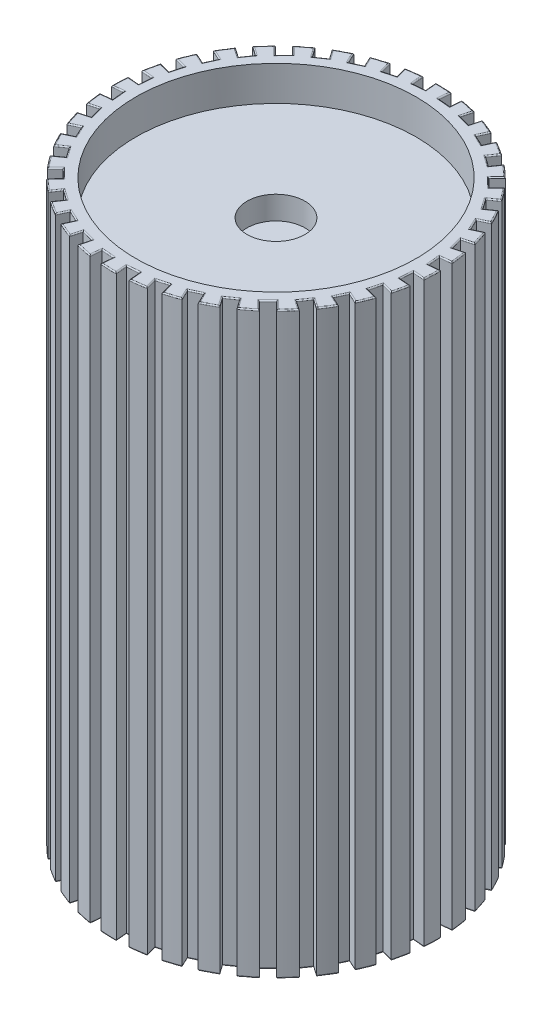
SolidWorks part; units mm, degrees
ref_plane "Front Plane" through (0, 0, 0) normal (0, 0, 1) x (1, 0, 0)
ref_plane "Top Plane" through (0, 0, 0) normal (0, 1, 0) x (1, 0, 0)
ref_plane "Right Plane" through (0, 0, 0) normal (1, 0, 0) x (0, 0, -1)
other "Configuration Table"
sketch "草图1" plane through (0, 0, 0) normal (0, 1, 0) x (1, 0, 0)
  circle A0 centre (0, 0) radius 13
  dimension "D1" = 26
extrude "凸台-拉伸1" add sketch "草图1" along normal blind 50
sketch "草图6" plane through (0, 50, 0) normal (0, 1, 0) x (1, 0, 0)
  circle A0 centre (0, 0) radius 14
  dimension "D1" = 28
extrude "凸台-拉伸4" add sketch "草图6" against normal through all
sketch "草图2" plane through (0, 50, 0) normal (0, 1, 0) x (1, 0, 0)
  circle A0 centre (0, 0) radius 12
  dimension "D1" = 24
extrude "切除-拉伸1" cut sketch "草图2" against normal blind 3
sketch "草图7" plane through (0, 50, 0) normal (0, 1, 0) x (1, 0, 0)
  line L0 (-15.6468, 4.1422) -> (-12.5671, 3.3269)
  line L1 (-15.6468, 4.1422) -> (-15.3762, 5.1646)
  line L2 (-12.5671, 3.3269) -> (-12.2964, 4.3493)
  line L3 (-15.3762, 5.1646) -> (-12.2964, 4.3493)
  line L4 (-14.6898, 6.7963) -> (-11.7985, 5.4586)
  line L5 (-14.6898, 6.7963) -> (-14.2457, 7.7562)
  line L6 (-14.2457, 7.7562) -> (-11.3544, 6.4185)
  line L7 (-11.7985, 5.4586) -> (-11.3544, 6.4185)
  line L8 (-13.2865, 9.2439) -> (-10.6713, 7.4245)
  line L9 (-13.2865, 9.2439) -> (-12.6825, 10.1121)
  line L10 (-12.6825, 10.1121) -> (-10.0673, 8.2926)
  line L11 (-10.6713, 7.4245) -> (-10.0673, 8.2926)
  line L12 (-11.4794, 11.4107) -> (-9.22, 9.1647)
  line L13 (-11.4794, 11.4107) -> (-10.7338, 12.1608)
  line L14 (-10.7338, 12.1608) -> (-8.4744, 9.9148)
  line L15 (-9.22, 9.1647) -> (-8.4744, 9.9148)
  line L16 (-9.3236, 13.2307) -> (-7.4884, 10.6265)
  line L17 (-9.3236, 13.2307) -> (-8.4591, 13.8399)
  line L18 (-8.4591, 13.8399) -> (-6.6239, 11.2358)
  line L19 (-7.4884, 10.6265) -> (-6.6239, 11.2358)
  line L20 (-6.8845, 14.6487) -> (-5.5294, 11.7654)
  line L21 (-6.8845, 14.6487) -> (-5.9273, 15.0986)
  line L22 (-5.9273, 15.0986) -> (-4.5722, 12.2153)
  line L23 (-5.5294, 11.7654) -> (-4.5722, 12.2153)
  line L24 (-4.2361, 15.6217) -> (-3.4024, 12.5469)
  line L25 (-4.2361, 15.6217) -> (-3.2154, 15.8985)
  line L26 (-3.2154, 15.8985) -> (-2.3816, 12.8237)
  line L27 (-3.4024, 12.5469) -> (-2.3816, 12.8237)
  line L28 (-1.4591, 16.1199) -> (-1.1719, 12.9471)
  line L29 (-1.4591, 16.1199) -> (-0.4058, 16.2153)
  line L30 (-0.4058, 16.2153) -> (-0.1186, 13.0424)
  line L31 (-1.1719, 12.9471) -> (-0.1186, 13.0424)
  line L32 (1.3622, 16.1284) -> (1.0941, 12.9539)
  line L33 (1.3622, 16.1284) -> (2.4161, 16.0394)
  line L34 (2.4161, 16.0394) -> (2.148, 12.8649)
  line L35 (1.0941, 12.9539) -> (2.148, 12.8649)
  line L36 (4.1422, 15.6468) -> (3.3269, 12.5671)
  line L37 (4.1422, 15.6468) -> (5.1646, 15.3762)
  line L38 (5.1646, 15.3762) -> (4.3493, 12.2964)
  line L39 (3.3269, 12.5671) -> (4.3493, 12.2964)
  line L40 (6.7963, 14.6898) -> (5.4586, 11.7985)
  line L41 (6.7963, 14.6898) -> (7.7562, 14.2457)
  line L42 (7.7562, 14.2457) -> (6.4185, 11.3544)
  line L43 (5.4586, 11.7985) -> (6.4185, 11.3544)
  line L44 (9.2439, 13.2865) -> (7.4245, 10.6713)
  line L45 (9.2439, 13.2865) -> (10.1121, 12.6825)
  line L46 (10.1121, 12.6825) -> (8.2926, 10.0673)
  line L47 (7.4245, 10.6713) -> (8.2926, 10.0673)
  line L48 (11.4107, 11.4794) -> (9.1647, 9.22)
  line L49 (11.4107, 11.4794) -> (12.1608, 10.7338)
  line L50 (12.1608, 10.7338) -> (9.9148, 8.4744)
  line L51 (9.1647, 9.22) -> (9.9148, 8.4744)
  line L52 (13.2307, 9.3236) -> (10.6265, 7.4884)
  line L53 (13.2307, 9.3236) -> (13.8399, 8.4591)
  line L54 (13.8399, 8.4591) -> (11.2358, 6.6239)
  line L55 (10.6265, 7.4884) -> (11.2358, 6.6239)
  line L56 (14.6487, 6.8845) -> (11.7654, 5.5294)
  line L57 (14.6487, 6.8845) -> (15.0986, 5.9273)
  line L58 (15.0986, 5.9273) -> (12.2153, 4.5722)
  line L59 (11.7654, 5.5294) -> (12.2153, 4.5722)
  line L60 (15.6217, 4.2361) -> (12.5469, 3.4024)
  line L61 (15.6217, 4.2361) -> (15.8985, 3.2154)
  line L62 (15.8985, 3.2154) -> (12.8237, 2.3816)
  line L63 (12.5469, 3.4024) -> (12.8237, 2.3816)
  line L64 (16.1199, 1.4591) -> (12.9471, 1.1719)
  line L65 (16.1199, 1.4591) -> (16.2153, 0.4058)
  line L66 (16.2153, 0.4058) -> (13.0424, 0.1186)
  line L67 (12.9471, 1.1719) -> (13.0424, 0.1186)
  line L68 (16.1284, -1.3622) -> (12.9539, -1.0941)
  line L69 (16.1284, -1.3622) -> (16.0394, -2.4161)
  line L70 (16.0394, -2.4161) -> (12.8649, -2.148)
  line L71 (12.9539, -1.0941) -> (12.8649, -2.148)
  line L72 (15.6468, -4.1422) -> (12.5671, -3.3269)
  line L73 (15.6468, -4.1422) -> (15.3762, -5.1646)
  line L74 (15.3762, -5.1646) -> (12.2964, -4.3493)
  line L75 (12.5671, -3.3269) -> (12.2964, -4.3493)
  line L76 (14.6898, -6.7963) -> (11.7985, -5.4586)
  line L77 (14.6898, -6.7963) -> (14.2457, -7.7562)
  line L78 (14.2457, -7.7562) -> (11.3544, -6.4185)
  line L79 (11.7985, -5.4586) -> (11.3544, -6.4185)
  line L80 (13.2865, -9.2439) -> (10.6713, -7.4245)
  line L81 (13.2865, -9.2439) -> (12.6825, -10.1121)
  line L82 (12.6825, -10.1121) -> (10.0673, -8.2926)
  line L83 (10.6713, -7.4245) -> (10.0673, -8.2926)
  line L84 (11.4794, -11.4107) -> (9.22, -9.1647)
  line L85 (11.4794, -11.4107) -> (10.7338, -12.1608)
  line L86 (10.7338, -12.1608) -> (8.4744, -9.9148)
  line L87 (9.22, -9.1647) -> (8.4744, -9.9148)
  line L88 (9.3236, -13.2307) -> (7.4884, -10.6265)
  line L89 (9.3236, -13.2307) -> (8.4591, -13.8399)
  line L90 (8.4591, -13.8399) -> (6.6239, -11.2358)
  line L91 (7.4884, -10.6265) -> (6.6239, -11.2358)
  line L92 (6.8845, -14.6487) -> (5.5294, -11.7654)
  line L93 (6.8845, -14.6487) -> (5.9273, -15.0986)
  line L94 (5.9273, -15.0986) -> (4.5722, -12.2153)
  line L95 (5.5294, -11.7654) -> (4.5722, -12.2153)
  line L96 (4.2361, -15.6217) -> (3.4024, -12.5469)
  line L97 (4.2361, -15.6217) -> (3.2154, -15.8985)
  line L98 (3.2154, -15.8985) -> (2.3816, -12.8237)
  line L99 (3.4024, -12.5469) -> (2.3816, -12.8237)
  line L100 (1.4591, -16.1199) -> (1.1719, -12.9471)
  line L101 (1.4591, -16.1199) -> (0.4058, -16.2153)
  line L102 (0.4058, -16.2153) -> (0.1186, -13.0424)
  line L103 (1.1719, -12.9471) -> (0.1186, -13.0424)
  line L104 (-1.3622, -16.1284) -> (-1.0941, -12.9539)
  line L105 (-1.3622, -16.1284) -> (-2.4161, -16.0394)
  line L106 (-2.4161, -16.0394) -> (-2.148, -12.8649)
  line L107 (-1.0941, -12.9539) -> (-2.148, -12.8649)
  line L108 (-4.1422, -15.6468) -> (-3.3269, -12.5671)
  line L109 (-4.1422, -15.6468) -> (-5.1646, -15.3762)
  line L110 (-5.1646, -15.3762) -> (-4.3493, -12.2964)
  line L111 (-3.3269, -12.5671) -> (-4.3493, -12.2964)
  line L112 (-6.7963, -14.6898) -> (-5.4586, -11.7985)
  line L113 (-6.7963, -14.6898) -> (-7.7562, -14.2457)
  line L114 (-7.7562, -14.2457) -> (-6.4185, -11.3544)
  line L115 (-5.4586, -11.7985) -> (-6.4185, -11.3544)
  line L116 (-9.2439, -13.2865) -> (-7.4245, -10.6713)
  line L117 (-9.2439, -13.2865) -> (-10.1121, -12.6825)
  line L118 (-10.1121, -12.6825) -> (-8.2926, -10.0673)
  line L119 (-7.4245, -10.6713) -> (-8.2926, -10.0673)
  line L120 (-11.4107, -11.4794) -> (-9.1647, -9.22)
  line L121 (-11.4107, -11.4794) -> (-12.1608, -10.7338)
  line L122 (-12.1608, -10.7338) -> (-9.9148, -8.4744)
  line L123 (-9.1647, -9.22) -> (-9.9148, -8.4744)
  line L124 (-13.2307, -9.3236) -> (-10.6265, -7.4884)
  line L125 (-13.2307, -9.3236) -> (-13.8399, -8.4591)
  line L126 (-13.8399, -8.4591) -> (-11.2358, -6.6239)
  line L127 (-10.6265, -7.4884) -> (-11.2358, -6.6239)
  line L128 (-14.6487, -6.8845) -> (-11.7654, -5.5294)
  line L129 (-14.6487, -6.8845) -> (-15.0986, -5.9273)
  line L130 (-15.0986, -5.9273) -> (-12.2153, -4.5722)
  line L131 (-11.7654, -5.5294) -> (-12.2153, -4.5722)
  line L132 (-15.6217, -4.2361) -> (-12.5469, -3.4024)
  line L133 (-15.6217, -4.2361) -> (-15.8985, -3.2154)
  line L134 (-15.8985, -3.2154) -> (-12.8237, -2.3816)
  line L135 (-12.5469, -3.4024) -> (-12.8237, -2.3816)
  line L136 (-16.1199, -1.4591) -> (-12.9471, -1.1719)
  line L137 (-16.1199, -1.4591) -> (-16.2153, -0.4058)
  line L138 (-16.2153, -0.4058) -> (-13.0424, -0.1186)
  line L139 (-12.9471, -1.1719) -> (-13.0424, -0.1186)
  line L140 (-16.1284, 1.3622) -> (-12.9539, 1.0941)
  line L141 (-16.1284, 1.3622) -> (-16.0394, 2.4161)
  line L142 (-16.0394, 2.4161) -> (-12.8649, 2.148)
  line L143 (-12.9539, 1.0941) -> (-12.8649, 2.148)
  circle A0 centre (0, 0) radius 13 construction
  point P150 (0, 0)
  dimension "D1" = 26
  dimension "D2" = 36
extrude "切除-拉伸2" cut sketch "草图7" against normal through all
sketch "草图8" plane through (0, 47, 0) normal (0, 1, 0) x (1, 0, 0)
  circle A0 centre (0, 0) radius 2.5
  dimension "D1" = 5
extrude "切除-拉伸3" cut sketch "草图8" against normal blind 2
fillet "圆角6" radius 0.1 144 edges at (1.1362, 0, -13.4521) (0.4872, 0, -13.9915) (-0.1619, 0, -13.5205) (-0.6453, 0, -12.9947) (-1.217, 0, -13.445) (-1.9498, 0, -13.8636) (-2.5072, 0, -13.2869) (-2.892, 0, -12.6853) (-3.5332, 0, -13.0294) (-4.3276, 0, -13.3143) (-4.7764, 0, -12.6497) (-5.0508, 0, -11.9904) (-5.7421, 0, -12.218) (-6.5739, 0, -12.3606) (-6.9004, 0, -11.6281) (-7.0562, 0, -10.9311) (-7.7765, 0, -11.0352) (-8.6204, 0, -11.0313) (-8.8148, 0, -10.2532) (-8.8472, 0, -9.5398) (-9.5746, 0, -9.5172) (-10.405, 0, -9.3668) (-10.4613, 0, -8.5668) (-10.3693, 0, -7.8586) (-11.0818, 0, -7.71) (-11.8734, 0, -7.4177) (-11.79, 0, -6.62) (-11.5764, 0, -5.9386) (-12.2522, 0, -5.6686) (-12.9811, 0, -5.2432) (-12.7604, 0, -4.4722) (-12.4318, 0, -3.8381) (-13.0504, 0, -3.4549) (-13.6944, 0, -2.9094) (-13.3432, 0, -2.1884) (-12.9094, 0, -1.6211) (-13.4521, 0, -1.1362) (-13.9915, 0, -0.4872) (-13.5205, 0, 0.1619) (-12.9947, 0, 0.6453) (-13.445, 0, 1.217) (-13.8636, 0, 1.9498) (-13.2869, 0, 2.5072) (-12.6853, 0, 2.892) (-13.0294, 0, 3.5332) (-13.3143, 0, 4.3276) (-12.6497, 0, 4.7764) (-11.9904, 0, 5.0508) (-12.218, 0, 5.7421) (-12.3606, 0, 6.5739) (-11.6281, 0, 6.9004) (-10.9311, 0, 7.0562) (-11.0352, 0, 7.7765) (-11.0313, 0, 8.6204) (-10.2532, 0, 8.8148) (-9.5398, 0, 8.8472) (-9.5172, 0, 9.5746) (-9.3668, 0, 10.405) (-8.5668, 0, 10.4613) (-7.8586, 0, 10.3693) (-7.71, 0, 11.0818) (-7.4177, 0, 11.8734) (-6.62, 0, 11.79) (-5.9386, 0, 11.5764) (-5.6686, 0, 12.2522) (-5.2432, 0, 12.9811) (-4.4722, 0, 12.7604) (-3.8381, 0, 12.4318) (-3.4549, 0, 13.0504) (-2.9094, 0, 13.6944) (-2.1884, 0, 13.3432) (-1.6211, 0, 12.9094) (-1.1362, 0, 13.4521) (-0.4872, 0, 13.9915) (0.1619, 0, 13.5205) (0.6453, 0, 12.9947) (1.217, 0, 13.445) (1.9498, 0, 13.8636) (2.5072, 0, 13.2869) (2.892, 0, 12.6853) (3.5332, 0, 13.0294) (4.3276, 0, 13.3143) (4.7764, 0, 12.6497) (5.0508, 0, 11.9904) (5.7421, 0, 12.218) (6.5739, 0, 12.3606) (6.9004, 0, 11.6281) (7.0562, 0, 10.9311) (7.7765, 0, 11.0352) (8.6204, 0, 11.0313) (8.8148, 0, 10.2532) (8.8472, 0, 9.5398) (9.5746, 0, 9.5172) (10.405, 0, 9.3668) (10.4613, 0, 8.5668) (10.3693, 0, 7.8586) (11.0818, 0, 7.71) (11.8734, 0, 7.4177) (11.79, 0, 6.62) (11.5764, 0, 5.9386) (12.2522, 0, 5.6686) (12.9811, 0, 5.2432) (12.7604, 0, 4.4722) (12.4318, 0, 3.8381) (13.0504, 0, 3.4549) (13.6944, 0, 2.9094) (13.3432, 0, 2.1884) (12.9094, 0, 1.6211) (13.4521, 0, 1.1362) (13.9915, 0, 0.4872) (13.5205, 0, -0.1619) (12.9947, 0, -0.6453) (13.445, 0, -1.217) (13.8636, 0, -1.9498) (13.2869, 0, -2.5072) (12.6853, 0, -2.892) (13.0294, 0, -3.5332) (13.3143, 0, -4.3276) (12.6497, 0, -4.7764) (11.9904, 0, -5.0508) (12.218, 0, -5.7421) (12.3606, 0, -6.5739) (11.6281, 0, -6.9004) (10.9311, 0, -7.0562) (11.0352, 0, -7.7765) (11.0313, 0, -8.6204) (10.2532, 0, -8.8148) (9.5398, 0, -8.8472) (9.5172, 0, -9.5746) (9.3668, 0, -10.405) (8.5668, 0, -10.4613) (7.8586, 0, -10.3693) (7.71, 0, -11.0818) (7.4177, 0, -11.8734) (6.62, 0, -11.79) (5.9386, 0, -11.5764) (5.6686, 0, -12.2522) (5.2432, 0, -12.9811) (4.4722, 0, -12.7604) (3.8381, 0, -12.4318) (3.4549, 0, -13.0504) (2.9094, 0, -13.6944) (2.1884, 0, -13.3432) (1.6211, 0, -12.9094)
fillet "圆角7" radius 0.1 145 edges at (0, 50, 12) (2.9094, 50, -13.6944) (3.4549, 50, -13.0504) (3.8381, 50, -12.4318) (4.4722, 50, -12.7604) (5.2432, 50, -12.9811) (5.6686, 50, -12.2522) (5.9386, 50, -11.5764) (6.62, 50, -11.79) (7.4177, 50, -11.8734) (7.71, 50, -11.0818) (7.8586, 50, -10.3693) (8.5668, 50, -10.4613) (9.3668, 50, -10.405) (9.5172, 50, -9.5746) (9.5398, 50, -8.8472) (10.2532, 50, -8.8148) (11.0313, 50, -8.6204) (11.0352, 50, -7.7765) (10.9311, 50, -7.0562) (11.6281, 50, -6.9004) (12.3606, 50, -6.5739) (12.218, 50, -5.7421) (11.9904, 50, -5.0508) (12.6497, 50, -4.7764) (13.3143, 50, -4.3276) (13.0294, 50, -3.5332) (12.6853, 50, -2.892) (13.2869, 50, -2.5072) (13.8636, 50, -1.9498) (13.445, 50, -1.217) (12.9947, 50, -0.6453) (13.5205, 50, -0.1619) (13.9915, 50, 0.4872) (13.4521, 50, 1.1362) (12.9094, 50, 1.6211) (13.3432, 50, 2.1884) (13.6944, 50, 2.9094) (13.0504, 50, 3.4549) (12.4318, 50, 3.8381) (12.7604, 50, 4.4722) (12.9811, 50, 5.2432) (12.2522, 50, 5.6686) (11.5764, 50, 5.9386) (11.79, 50, 6.62) (11.8734, 50, 7.4177) (11.0818, 50, 7.71) (10.3693, 50, 7.8586) (10.4613, 50, 8.5668) (10.405, 50, 9.3668) (9.5746, 50, 9.5172) (8.8472, 50, 9.5398) (8.8148, 50, 10.2532) (8.6204, 50, 11.0313) (7.7765, 50, 11.0352) (7.0562, 50, 10.9311) (6.9004, 50, 11.6281) (6.5739, 50, 12.3606) (5.7421, 50, 12.218) (5.0508, 50, 11.9904) (4.7764, 50, 12.6497) (4.3276, 50, 13.3143) (3.5332, 50, 13.0294) (2.892, 50, 12.6853) (2.5072, 50, 13.2869) (1.9498, 50, 13.8636) (1.217, 50, 13.445) (0.6453, 50, 12.9947) (0.1619, 50, 13.5205) (-0.4872, 50, 13.9915) (-1.1362, 50, 13.4521) (-1.6211, 50, 12.9094) (-2.1884, 50, 13.3432) (-2.9094, 50, 13.6944) (-3.4549, 50, 13.0504) (-3.8381, 50, 12.4318) (-4.4722, 50, 12.7604) (-5.2432, 50, 12.9811) (-5.6686, 50, 12.2522) (-5.9386, 50, 11.5764) (-6.62, 50, 11.79) (-7.4177, 50, 11.8734) (-7.71, 50, 11.0818) (-7.8586, 50, 10.3693) (-8.5668, 50, 10.4613) (-9.3668, 50, 10.405) (-9.5172, 50, 9.5746) (-9.5398, 50, 8.8472) (-10.2532, 50, 8.8148) (-11.0313, 50, 8.6204) (-11.0352, 50, 7.7765) (-10.9311, 50, 7.0562) (-11.6281, 50, 6.9004) (-12.3606, 50, 6.5739) (-12.218, 50, 5.7421) (-11.9904, 50, 5.0508) (-12.6497, 50, 4.7764) (-13.3143, 50, 4.3276) (-13.0294, 50, 3.5332) (-12.6853, 50, 2.892) (-13.2869, 50, 2.5072) (-13.8636, 50, 1.9498) (-13.445, 50, 1.217) (-12.9947, 50, 0.6453) (-13.5205, 50, 0.1619) (-13.9915, 50, -0.4872) (-13.4521, 50, -1.1362) (-12.9094, 50, -1.6211) (-13.3432, 50, -2.1884) (-13.6944, 50, -2.9094) (-13.0504, 50, -3.4549) (-12.4318, 50, -3.8381) (-12.7604, 50, -4.4722) (-12.9811, 50, -5.2432) (-12.2522, 50, -5.6686) (-11.5764, 50, -5.9386) (-11.79, 50, -6.62) (-11.8734, 50, -7.4177) (-11.0818, 50, -7.71) (-10.3693, 50, -7.8586) (-10.4613, 50, -8.5668) (-10.405, 50, -9.3668) (-9.5746, 50, -9.5172) (-8.8472, 50, -9.5398) (-8.8148, 50, -10.2532) (-8.6204, 50, -11.0313) (-7.7765, 50, -11.0352) (-7.0562, 50, -10.9311) (-6.9004, 50, -11.6281) (-6.5739, 50, -12.3606) (-5.7421, 50, -12.218) (-5.0508, 50, -11.9904) (-4.7764, 50, -12.6497) (-4.3276, 50, -13.3143) (-3.5332, 50, -13.0294) (-2.892, 50, -12.6853) (-2.5072, 50, -13.2869) (-1.9498, 50, -13.8636) (-1.217, 50, -13.445) (-0.6453, 50, -12.9947) (-0.1619, 50, -13.5205) (0.4872, 50, -13.9915) (1.1362, 50, -13.4521) (1.6211, 50, -12.9094) (2.1884, 50, -13.3432)
sketch "草图9" plane through (0, 47, 0) normal (0, 1, 0) x (1, 0, 0)
  circle A0 centre (0, 0) radius 12.1
  circle A1 centre (0, 0) radius 12 construction
  dimension "D1" = 0.1
extrude "切除-拉伸4" cut sketch "草图9" along normal through all
